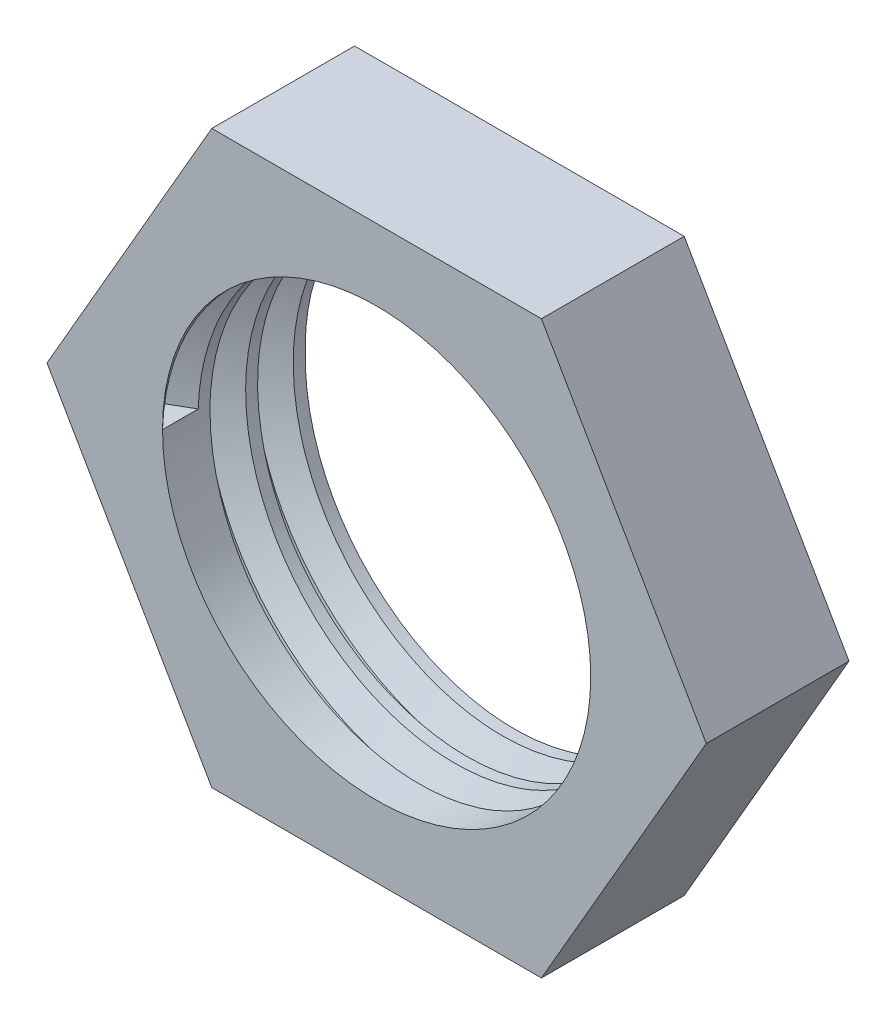
SolidWorks part; units mm, degrees
ref_plane "前视基准面" through (0, 0, 0) normal (0, 0, 1) x (1, 0, 0)
ref_plane "上视基准面" through (0, 0, 0) normal (0, 1, 0) x (1, 0, 0)
ref_plane "右视基准面" through (0, 0, 0) normal (1, 0, 0) x (0, 0, -1)
other "Configuration Table"
sketch "草图2" plane through (0, 0, 0) normal (0, 0, 1) x (1, 0, 0)
  line L1 (6.9282, 0) -> (3.4641, 6)
  line L2 (3.4641, 6) -> (-3.4641, 6)
  line L3 (-3.4641, 6) -> (-6.9282, 0)
  line L4 (-6.9282, 0) -> (-3.4641, -6)
  line L5 (-3.4641, -6) -> (3.4641, -6)
  line L6 (3.4641, -6) -> (6.9282, 0)
  circle A0 centre (0, 0) radius 6 construction
  circle A1 centre (0, 0) radius 4.5
extrude "凸台-拉伸1" add sketch "草图2" along normal blind 3
thread "螺纹线1" pitch 1 method cut profile "螺纹线轮廓4" start angle 0, offset 0, length 0, pitch 1, diameter 9
ref_plane "基准面4" through (-4.5, 0, 3) normal (0, -1, 0) x (-1, 0, 0)
sketch "螺纹线轮廓4" plane through (-4.5, 0, 3) normal (0, -1, 0) x (-1, 0, 0)
  line L0 (0, 0) -> (0, 1) construction
  line L1 (0, 0) -> (0.5413, 0.3125)
  line L2 (0.5413, 0.3125) -> (0.5413, 0.4375)
  line L3 (0.5413, 0.4375) -> (0, 0.75)
  line L4 (0.5413, 0.375) -> (0, 0.375) construction
  line L11 (0, 0) -> (0, 0.75)
  point P2 (0, 0)
  dimension "Pitch" = 1
  dimension "Profile_Angle" = 60
  dimension "Profile_Land" = 0.125
  dimension "Profile_Height" = 0.5413
